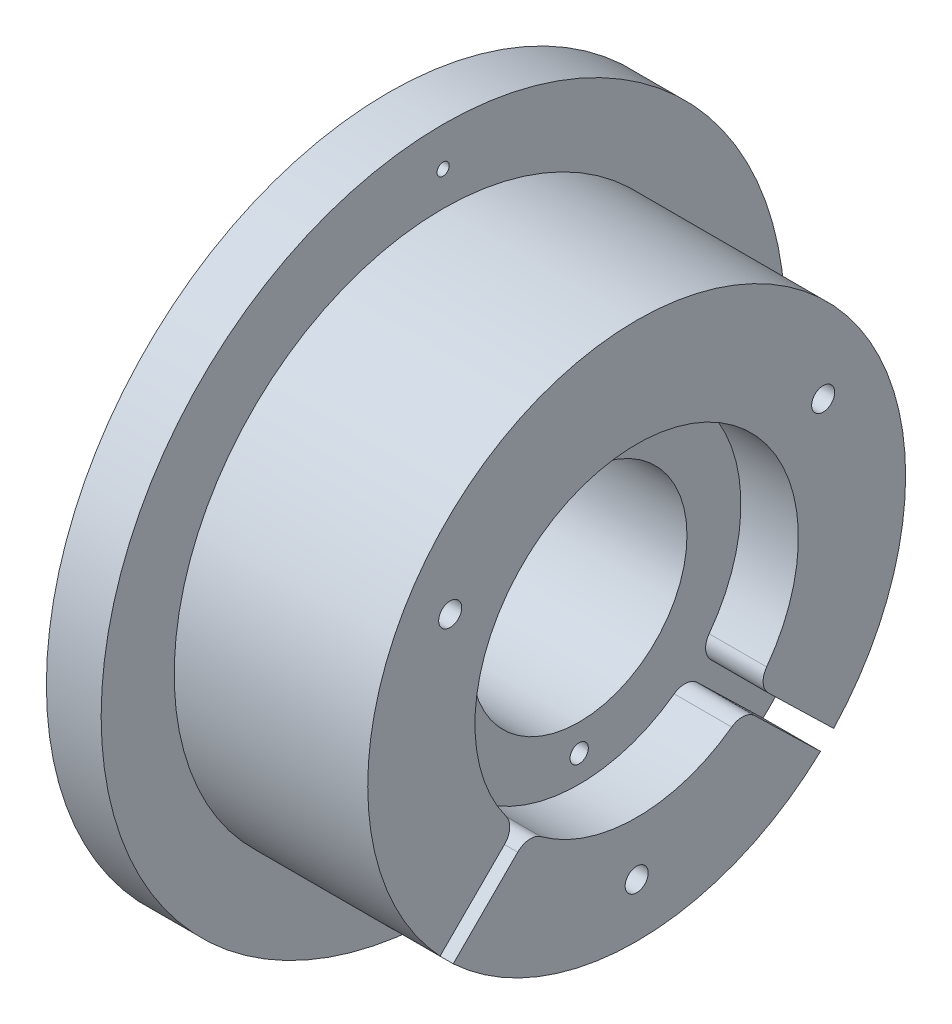
SolidWorks part; units mm, degrees
ref_plane "Front" through (0, 0, 0) normal (0, 0, 1) x (1, 0, 0)
ref_plane "Top" through (0, 0, 0) normal (0, 1, 0) x (1, 0, 0)
ref_plane "Right" through (0, 0, 0) normal (1, 0, 0) x (0, 0, -1)
sketch "Sketch1" plane through (0, 0, 0) normal (0, 0, 1) x (1, 0, 0)
  line L0 (0, 0) -> (0, 23.7871)
  line L1 (0, 23.7871) -> (3.81, 23.7871)
  line L2 (3.81, 23.7871) -> (3.81, 18.7071)
  line L3 (3.81, 18.7071) -> (17.272, 18.7071)
  line L4 (17.272, 18.7071) -> (17.272, 11.25)
  line L5 (17.272, 11.25) -> (13.272, 11.25)
  line L6 (13.272, 11.25) -> (13.272, 0)
  line L7 (13.272, 0) -> (0, 0)
  line L8 (13.272, 7.5) -> (0, 7.5)
  dimension "D1" = 23.7871
  dimension "D2" = 3.81
  dimension "D3" = 13.462
  dimension "D4" = 4
  dimension "D5" = 11.25
  dimension "D6" = 18.7071
  dimension "D7" = 7.5
revolve "Revolve1" add sketch "Sketch1" angle 360 about L7 region at (7.4749, 14.1825, 0)
sketch "Sketch2" plane through (17.272, 0, 0) normal (1, 0, 0) x (0, 0, -1)
  line L0 (0, 0) -> (-13.2279, -13.2279) construction
  line L1 (0, 0) -> (0, -18.7071) construction
  line L2 (0.2823, 0.2909) -> (13.7078, -12.7364)
  line L3 (-13.6875, -12.7683) -> (-12.7683, -13.6875)
  line L4 (-13.6875, -12.7683) -> (-0.4596, 0.4596)
  line L5 (-0.4596, 0.4596) -> (0.4596, -0.4596)
  line L6 (0.4596, -0.4596) -> (-12.7683, -13.6875)
  line L7 (12.8025, -13.6694) -> (13.7078, -12.7364)
  line L8 (12.8025, -13.6694) -> (-0.623, -0.642)
  line L9 (-0.623, -0.642) -> (0.2823, 0.2909)
  circle A0 centre (0, 0) radius 18.7071 construction
  circle A1 centre (-12.9709, 7.4887) radius 0.315
  circle A2 centre (12.9709, 7.4888) radius 0.315
  circle A3 centre (0, 0) radius 18.7071 construction
  circle A4 centre (0, -14.9775) radius 0.315
  point P6 (0, 0)
  point P14 (-13.2279, -13.2279)
  circle M8 centre (0, 0) radius 18.7071
  circle M9 centre (0, 0) radius 11.25
  dimension "D4" = 0.63
  dimension "D1" = 45
  dimension "D2" = 1.3
  dimension "D3" = 14.9775
  dimension "D5" = 3
  dimension "D6" = 2
extrude "Cut-Extrude1" cut sketch "Sketch2" against normal up to surface (4 mm away) contours L8 L9 L5 L4 L6 M9 | L6 L4 M9 M8 | L8 L2 M8 M9 | L9 L5 L6 L8 L2 M9 | A4 | A1 | A2 region at (17.272, -4.2339, -4.0243) region at (17.272, -10.6015, -10.574) region at (17.272, -4.115, 4.1339) region at (17.272, -10.5879, 10.5879) region at (17.272, 7.4887, 12.9709) region at (17.272, 7.4888, -12.9709) region at (17.272, -14.9775, 0) up to face at (13.272, 7.5, 0)
sketch "Sketch3" plane through (3.81, 0, 0) normal (1, 0, 0) x (0, 0, -1)
  line L0 (0, 0) -> (0, 21.082) construction
  circle A0 centre (0, 21.082) radius 0.425
  dimension "D1" = 0.85
  dimension "D2" = 21.082
extrude "Cut-Extrude2" cut sketch "Sketch3" against normal through all
sketch "Sketch4" plane through (13.272, 0, 0) normal (1, 0, 0) x (0, 0, -1)
  line L0 (0, -9.375) -> (0, 9.375) construction
  circle A0 centre (0, 9.375) radius 0.635
  circle A1 centre (0, -9.375) radius 0.635
  point P6 (0, 0)
  dimension "D2" = 1.27
  dimension "D1" = 18.75
extrude "Cut-Extrude3" cut sketch "Sketch4" against normal through all
fillet "Fillet1" radius 1.25 4 edges at (15.272, -7.482, 8.4013) (15.272, -8.4013, 7.482) (15.272, -8.4516, -7.4252) (15.272, -7.5383, -8.3508)
hole_wizard "M2x0.4 Tapped Hole1" positions "3DSketch2" profile "Sketch5" tap size "M2x0.4" standard "ANSI Metric"
sketch3d "3DSketch2"
  line L0 (13.272, 7.4887, 12.9709) -> (17.272, 7.4887, 12.9709) construction
  line L1 (13.272, 7.4888, -12.9709) -> (17.272, 7.4888, -12.9709) construction
  line L2 (13.272, -14.9775, 0) -> (17.272, -14.9775, 0) construction
  point P0 (17.272, 7.4887, 12.9709)
  point P4 (17.272, 7.4888, -12.9709)
  point P8 (17.272, -14.9775, 0)
sketch "Sketch5" plane through (17.272, 7.4887, 12.9709) normal (0, 1, 0) x (0, 0, -1)
  line L0 (0, 0) -> (0, 6.8307)
  line L1 (0, 6.8307) -> (0.8, 6.35)
  line L2 (0.8, 6.35) -> (0.8, 0)
  line L5 (0.8, 0) -> (0, 0)
  line L10 (0, 6.8307) -> (-0.8, 6.35) construction
  line L11 (0, -6.35) -> (0, 107.95) construction
  dimension "Tap Drill Dia." = 1.6
  dimension "Tap Drill Depth" = 6.35
  dimension "Drill Angle" = 118
cosmetic thread "Hole Thread1" parameters "D1"=4, "D2"=2
cosmetic thread "Hole Thread2" parameters "D1"=4, "D2"=2
cosmetic thread "Hole Thread3" parameters "D1"=4, "D2"=2
